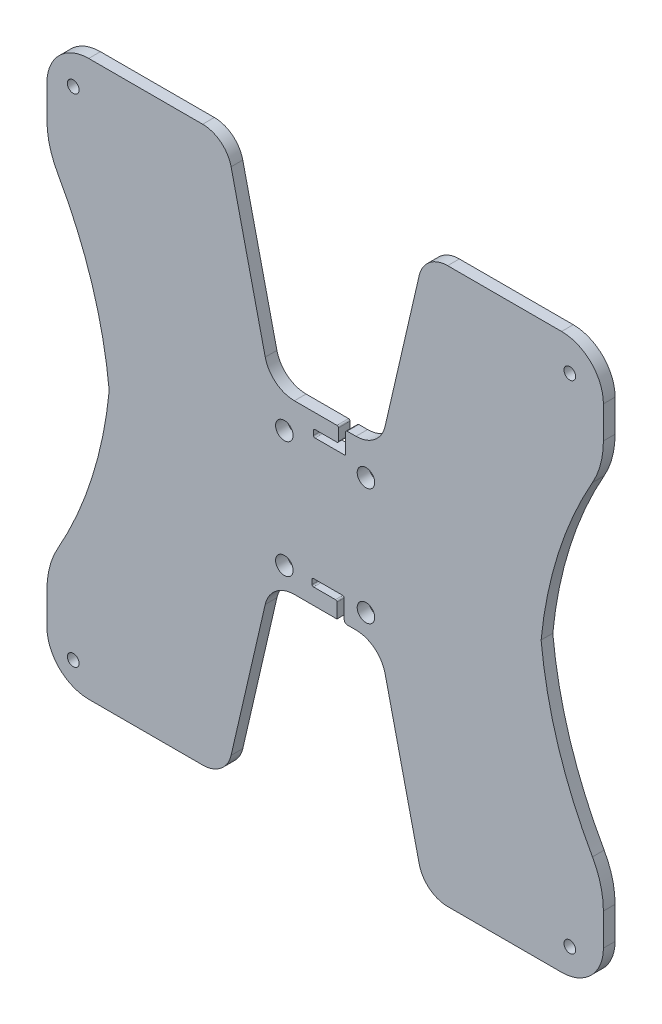
SolidWorks part; units mm, degrees
ref_plane "Front Plane" through (0, 0, 0) normal (0, 0, 1) x (1, 0, 0)
ref_plane "Top Plane" through (0, 0, 0) normal (0, 1, 0) x (1, 0, 0)
ref_plane "Right Plane" through (0, 0, 0) normal (1, 0, 0) x (0, 0, -1)
sketch "Sketch2" plane through (0, 0, 0) normal (0, 0, 1) x (1, 0, 0)
  line L3 (94.3754, -52.7044) -> (94.3754, -56.7044)
  line L4 (93.8754, -57.2044) -> (86.3754, -57.2044)
  line L5 (85.8754, -57.7044) -> (85.8754, -59.2044)
  line L6 (86.3754, -59.7044) -> (96.3754, -59.7044)
  line L7 (96.8754, -59.2044) -> (96.8754, -52.7044)
  line L8 (97.3754, -52.2044) -> (100.3754, -52.2044)
  line L9 (110.3627, -44.2602) -> (122.0425, 6.3307)
  line L10 (131.7862, 14.0812) -> (170.7845, 14.0812)
  line L11 (185.0955, -0.2297) -> (185.0955, -11.2297)
  line L16 (96.3754, -108.6331) -> (96.3754, -102.1331)
  line L17 (95.8754, -101.6331) -> (85.8754, -101.6331)
  line L18 (85.3754, -102.1331) -> (85.3754, -103.6331)
  line L19 (85.8754, -104.1331) -> (93.3754, -104.1331)
  line L20 (93.8754, -104.6331) -> (93.8754, -108.6331)
  line L26 (163.7717, -80.9188) -> (-81.9172, -80.9188) construction
  line L27 (97.3754, -109.6331) -> (100.3754, -109.6331)
  line L28 (185.0955, -161.6078) -> (185.0955, -150.6078)
  line L29 (131.7862, -175.9188) -> (170.7845, -175.9188)
  line L30 (110.3627, -117.5774) -> (122.0425, -168.1683)
  line L31 (185.0955, -161.6078) -> (-5.4045, -161.6078) construction
  line L32 (89.8455, -161.6078) -> (89.8455, -80.9188) construction
  line L33 (82.3155, -52.2044) -> (79.3155, -52.2044)
  line L34 (82.3155, -109.6331) -> (79.3155, -109.6331)
  line L35 (15.9192, -80.9188) -> (261.6081, -80.9188) construction
  line L36 (69.3282, -117.5774) -> (57.6484, -168.1683)
  line L37 (47.9047, -175.9188) -> (8.9064, -175.9188)
  line L38 (-5.4045, -161.6078) -> (-5.4045, -150.6078)
  line L39 (-5.4045, -0.2297) -> (-5.4045, -11.2297)
  line L40 (47.9047, 14.0812) -> (8.9064, 14.0812)
  line L41 (69.3282, -44.2602) -> (57.6484, 6.3307)
  line L42 (82.3155, -52.2044) -> (93.8754, -52.2044)
  line L43 (82.3155, -109.6331) -> (93.8754, -109.6331)
  line L44 (93.8754, -108.6331) -> (93.8754, -109.6331)
  line L45 (142.4554, -175.9188) -> (142.4554, 14.0812) construction
  arc A2 (94.3754, -52.7044) -> (93.8754, -52.2044) centre (93.8754, -52.7044) ccw
  arc A3 (93.8754, -57.2044) -> (94.3754, -56.7044) centre (93.8754, -56.7044) ccw
  arc A5 (85.8754, -59.2044) -> (86.3754, -59.7044) centre (86.3754, -59.2044) ccw
  arc A6 (86.3754, -57.2044) -> (85.8754, -57.7044) centre (86.3754, -57.7044) ccw
  arc A7 (96.3754, -59.7044) -> (96.8754, -59.2044) centre (96.3754, -59.2044) ccw
  arc A8 (97.3754, -52.2044) -> (96.8754, -52.7044) centre (97.3754, -52.7044) ccw
  arc A9 (100.3754, -52.2044) -> (110.3627, -44.2602) centre (100.3754, -41.9544) ccw
  arc A10 (131.7862, 14.0812) -> (122.0425, 6.3307) centre (131.7862, 4.0812) ccw
  arc A11 (185.0955, -0.2297) -> (170.7845, 14.0812) centre (170.7845, -0.2297) ccw
  arc A12 (181.353, -25.4269) -> (185.0955, -11.2297) centre (156.2955, -11.2297) ccw
  arc A13 (181.353, -25.4269) -> (163.7717, -80.9188) centre (303.5955, -94.6875) ccw
  arc A18 (96.3754, -108.6331) -> (97.3754, -109.6331) centre (97.3754, -108.6331) ccw
  arc A19 (96.3754, -102.1331) -> (95.8754, -101.6331) centre (95.8754, -102.1331) ccw
  arc A20 (85.8754, -101.6331) -> (85.3754, -102.1331) centre (85.8754, -102.1331) ccw
  arc A21 (85.3754, -103.6331) -> (85.8754, -104.1331) centre (85.8754, -103.6331) ccw
  arc A22 (93.8754, -104.6331) -> (93.3754, -104.1331) centre (93.3754, -104.6331) ccw
  arc A31 (79.3155, -109.6331) -> (69.3282, -117.5774) centre (79.3155, -119.8831) ccw
  arc A32 (181.353, -136.4106) -> (163.7717, -80.9188) centre (303.5955, -67.15) cw
  arc A33 (181.353, -136.4106) -> (185.0955, -150.6078) centre (156.2955, -150.6078) cw
  arc A34 (185.0955, -161.6078) -> (170.7845, -175.9188) centre (170.7845, -161.6078) cw
  arc A35 (131.7862, -175.9188) -> (122.0425, -168.1683) centre (131.7862, -165.9188) cw
  arc A36 (100.3754, -109.6331) -> (110.3627, -117.5774) centre (100.3754, -119.8831) cw
  arc A37 (47.9047, -175.9188) -> (57.6484, -168.1683) centre (47.9047, -165.9188) ccw
  arc A38 (-5.4045, -161.6078) -> (8.9064, -175.9188) centre (8.9064, -161.6078) ccw
  arc A39 (-1.6621, -136.4106) -> (-5.4045, -150.6078) centre (23.3955, -150.6078) ccw
  arc A40 (-1.6621, -136.4106) -> (15.9192, -80.9188) centre (-123.9045, -67.15) ccw
  arc A41 (-1.6621, -25.4269) -> (15.9192, -80.9188) centre (-123.9045, -94.6875) cw
  arc A42 (-1.6621, -25.4269) -> (-5.4045, -11.2297) centre (23.3955, -11.2297) cw
  arc A43 (-5.4045, -0.2297) -> (8.9064, 14.0812) centre (8.9064, -0.2297) cw
  arc A44 (47.9047, 14.0812) -> (57.6484, 6.3307) centre (47.9047, 4.0812) cw
  arc A45 (79.3155, -52.2044) -> (69.3282, -44.2602) centre (79.3155, -41.9544) cw
  dimension "D6" = 190.5
  dimension "D8" = 1
  dimension "D9" = 1
  dimension "D12" = 1
  dimension "D13" = 1
  dimension "D17" = 1
  dimension "D18" = 1
  dimension "D40" = 2
  dimension "D42" = 1
  dimension "D44" = 1
  dimension "D45" = 1
  dimension "D48" = 1
  dimension "D5" = 190
  dimension "D10" = 7.5
  dimension "D11" = 4
  dimension "D14" = 1.5
  dimension "D15" = 2.5
  dimension "D16" = 10
  dimension "D19" = 6.5
  dimension "D20" = 3
  dimension "D25" = 103
  dimension "D30" = 118.5
  dimension "D41" = 6.5
  dimension "D43" = 10
  dimension "D46" = 1.5
  dimension "D47" = 7.5
  dimension "D49" = 4
extrude "Boss-Extrude1" add sketch "Sketch2" along normal blind 4
sketch "Sketch3" plane through (0, 0, 4) normal (0, 0, 1) x (1, 0, 0)
  line L0 (170.7845, 14.0812) -> (131.7862, 14.0812) construction
  line L1 (-5.4045, -0.2297) -> (-5.4045, -11.2297) construction
  line L2 (8.9064, 14.0812) -> (170.7845, 14.0812) construction
  line L3 (89.8455, 14.0812) -> (89.8455, -175.9188) construction
  line L4 (75.8755, -62.7419) -> (103.8155, -62.7419) construction
  line L5 (8.9064, -175.9188) -> (170.7845, -175.9188) construction
  circle A0 centre (3.5955, 3.0812) radius 2
  circle A1 centre (3.5955, -166.9188) radius 2
  circle A2 centre (75.8755, -62.7419) radius 3
  circle A3 centre (103.8155, -62.7419) radius 3
  circle A4 centre (75.8755, -102.7419) radius 3
  circle A5 centre (103.8155, -102.7419) radius 3
  circle A6 centre (173.5955, -166.9188) radius 2
  circle A7 centre (173.5955, 3.0812) radius 2
  arc A8 (170.7845, -175.9188) -> (185.0955, -161.6078) centre (170.7845, -161.6078) ccw construction
  point P20 (89.8455, -62.7419)
  point P28 (0, 0)
  point P34 (0, 0)
  dimension "D1" = 170
  dimension "D3" = 170
  dimension "D4" = 11
  dimension "D5" = 27.94
  dimension "D6" = 40
  dimension "D7" = 9
  dimension "D8" = 6
  dimension "D9" = 6
  dimension "D10" = 6
  dimension "D11" = 6
extrude "Cut-Extrude1" cut sketch "Sketch3" against normal blind 4
ref_plane "Plane1" through (8.9064, 14.0812, 4) normal (-1, 0, 0) x (0, 0, 1)
sketch "Sketch5" plane through (0, 0, 4) normal (0, 0, 1) x (1, 0, 0)
  line L0 (47.9047, 14.0812) -> (8.9064, 14.0812) construction
  line L3 (44.9827, 14.0812) -> (44.9827, -175.9188) construction
  line L4 (8.9064, -175.9188) -> (47.9047, -175.9188) construction
  line L5 (-5.4045, -11.2297) -> (185.0955, -11.2297) construction
